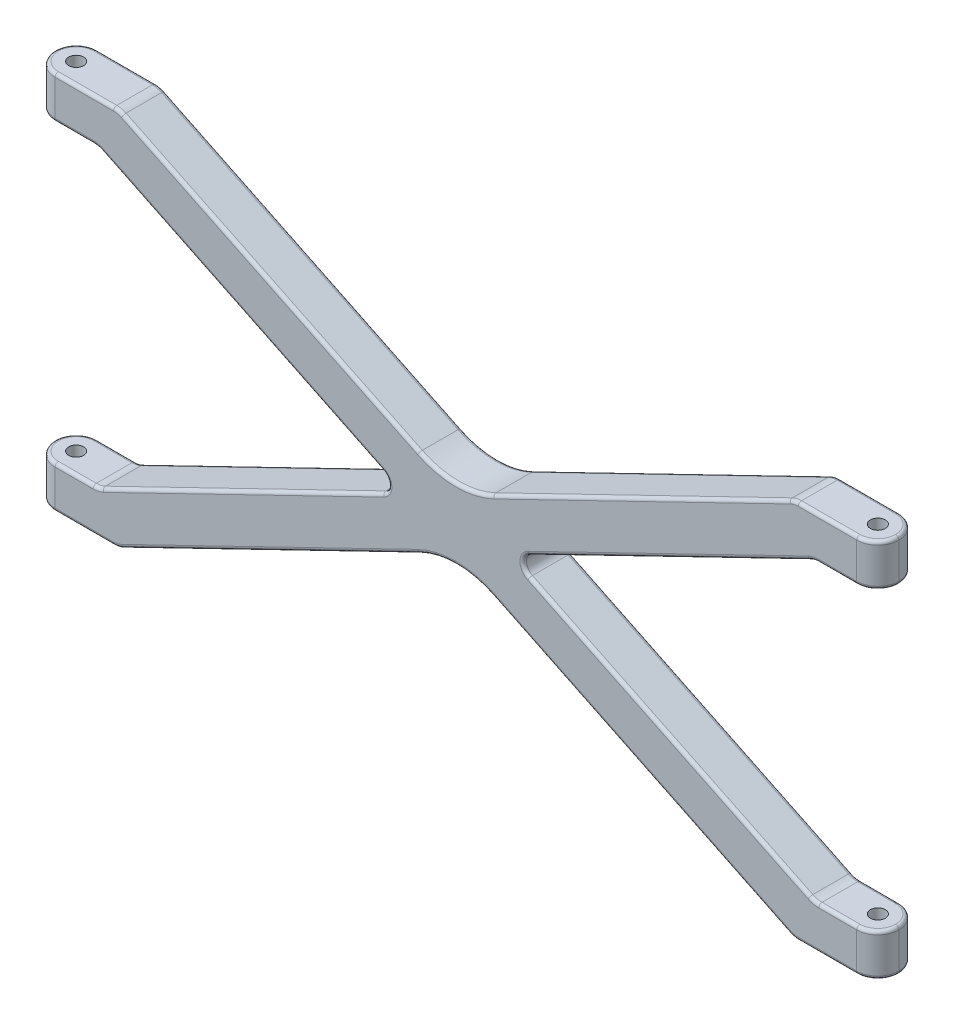
SolidWorks part; units mm, degrees
ref_plane "Front Plane" through (0, 0, 0) normal (0, 0, 1) x (1, 0, 0)
ref_plane "Top Plane" through (0, 0, 0) normal (0, 1, 0) x (1, 0, 0)
ref_plane "Right Plane" through (0, 0, 0) normal (1, 0, 0) x (0, 0, -1)
sketch "Sketch1" plane through (0, 0, 0) normal (0, 0, 1) x (1, 0, 0)
  line L0 (101.6, -57.15) -> (-107.7631, 44.45)
  line L1 (101.6, -57.15) -> (-101.6, -57.15) construction
  line L2 (101.6, -57.15) -> (101.6, 57.15) construction
  line L3 (101.6, 57.15) -> (-101.6, 57.15) construction
  line L4 (-101.6, -57.15) -> (-101.6, 57.15) construction
  line L5 (101.6, -57.15) -> (-101.6, 57.15) construction
  line L6 (101.6, 57.15) -> (-101.6, -57.15) construction
  line L7 (101.6, -57.15) -> (107.7631, -44.45) construction
  line L8 (-107.7631, 44.45) -> (-101.6, 57.15) construction
  line L9 (107.7631, -44.45) -> (-101.6, 57.15)
  line L10 (101.6, -57.15) -> (-101.6, 57.15) construction
  line L11 (-107.7631, 44.45) -> (107.7631, -44.45) construction
  line L12 (-107.7631, -44.45) -> (101.6, 57.15)
  line L13 (-107.7631, -44.45) -> (-101.6, -57.15) construction
  line L14 (101.6, 57.15) -> (107.7631, 44.45) construction
  line L15 (-101.6, -57.15) -> (107.7631, 44.45)
  line L16 (-107.7631, -44.45) -> (107.7631, 44.45) construction
  line L17 (101.6, 57.15) -> (-101.6, -57.15) construction
  line L18 (101.6, 57.15) -> (127, 57.15)
  line L19 (127, 57.15) -> (127, 44.45)
  line L20 (127, 44.45) -> (107.7631, 44.45)
  line L21 (-101.6, 57.15) -> (-127, 57.15)
  line L22 (-127, 57.15) -> (-127, 44.45)
  line L23 (-127, 44.45) -> (-107.7631, 44.45)
  line L24 (-101.6, -57.15) -> (-127, -57.15)
  line L25 (-127, -57.15) -> (-127, -44.45)
  line L26 (-127, -44.45) -> (-107.7631, -44.45)
  line L27 (101.6, -57.15) -> (127, -57.15)
  line L28 (127, -57.15) -> (127, -44.45)
  line L29 (127, -44.45) -> (107.7631, -44.45)
  point P0 (0, 0)
  point P1 (-127, -50.8)
  point P7 (0, 0)
  point P8 (0, 0)
  dimension "D1" = 114.3
  dimension "D2" = 203.2
  dimension "D4" = 12.7
  dimension "D5" = 254
  dimension "D6" = 254
  dimension "D7" = 25.4
extrude "Boss-Extrude1" add sketch "Sketch1" along normal blind 12.7 contours L22 L23 L0 L12 L9 L21 | L20 L19 L18 L12 L9 L15 | L28 L29 L9 L15 L0 L27 | L26 L25 L24 L15 L0 L12 | L0 L15 L9 L12 region at (65.6574, -31.1747, 0) region at (-65.6574, -31.1747, 0) region at (0, 0, 0) region at (-65.6574, 31.1747, 0) region at (65.6574, 31.1747, 0)
fillet "Fillet1" radius 6.35 8 edges at (127, -50.8, 0) (127, -50.8, 12.7) (127, 50.8, 0) (127, 50.8, 12.7) (-127, 50.8, 12.7) (-127, 50.8, 0) (-127, -50.8, 0) (-127, -50.8, 12.7)
sketch "Sketch2" plane through (0, -57.15, 0) normal (0, -1, 0) x (1, 0, 0)
  circle A0 centre (-120.65, 6.35) radius 2.25
  circle A1 centre (120.65, 6.35) radius 2.25
  dimension "D1" = 4.5
extrude "Cut-Extrude1" cut sketch "Sketch2" against normal through all
fillet "Fillet4" radius 25.4 2 edges at (0, 7.8454, 6.35) (0, -7.8454, 6.35)
fillet "Fillet5" radius 3.175 2 edges at (16.1667, 0, 6.35) (-16.1667, 0, 6.35)
fillet "Fillet2" radius 6.35 8 edges at (101.6, -57.15, 6.35) (107.7631, -44.45, 6.35) (107.7631, 44.45, 6.35) (101.6, 57.15, 6.35) (-101.6, 57.15, 6.35) (-107.7631, -44.45, 6.35) (-107.7631, 44.45, 6.35) (-101.6, -57.15, 6.35)
fillet "Fillet3" radius 1 72 edges at (-55.6882, 34.8699, 12.7) (-101.6371, 56.9887, 12.7) (-111.8547, 57.15, 12.7) (-125.1401, 57.15, 10.8401) (-125.1401, 57.15, 1.8599) (-111.8547, 57.15, 0) (-101.6371, 56.9887, 0) (-55.6882, 34.8699, 0) (55.6882, 34.8699, 0) (101.6371, 56.9887, 0) (111.8547, 57.15, 0) (125.1401, 57.15, 1.8599) (125.1401, 57.15, 10.8401) (111.8547, 57.15, 12.7) (101.6371, 56.9887, 12.7) (101.6371, -56.9887, 12.7) (111.8547, -57.15, 12.7) (125.1401, -57.15, 10.8401) (125.1401, -57.15, 1.8599) (111.8547, -57.15, 0) (101.6371, -56.9887, 0) (55.6882, -34.8699, 0) (-55.6882, -34.8699, 0) (-101.6371, -56.9887, 0) (-111.8547, -57.15, 0) (-125.1401, -57.15, 1.8599) (-125.1401, -57.15, 10.8401) (-111.8547, -57.15, 12.7) (-101.6371, -56.9887, 12.7) (-55.6882, -34.8699, 12.7) (64.2515, -23.3346, 12.7) (107.8002, -44.2887, 12.7) (114.9362, -44.45, 12.7) (125.1401, -44.45, 10.8401) (125.1401, -44.45, 1.8599) (114.9362, -44.45, 0) (107.8002, -44.2887, 0) (64.2515, -23.3346, 0) (64.2515, 23.3346, 0) (107.8002, 44.2887, 0) (114.9362, 44.45, 0) (125.1401, 44.45, 1.8599) (125.1401, 44.45, 10.8401) (114.9362, 44.45, 12.7) (107.8002, 44.2887, 12.7) (-64.2515, -23.3346, 12.7) (-107.8002, -44.2887, 12.7) (-114.9362, -44.45, 12.7) (-125.1401, -44.45, 10.8401) (-125.1401, -44.45, 1.8599) (-114.9362, -44.45, 0) (-107.8002, -44.2887, 0) (-64.2515, -23.3346, 0) (-64.2515, 23.3346, 0) (-107.8002, 44.2887, 0) (-114.9362, 44.45, 0) (-125.1401, 44.45, 1.8599) (-125.1401, 44.45, 10.8401) (-114.9362, 44.45, 12.7) (-107.8002, 44.2887, 12.7) (55.6882, 34.8699, 12.7) (55.6882, -34.8699, 12.7) (64.2515, 23.3346, 12.7) (-64.2515, 23.3346, 12.7) (0, 10.6783, 12.7) (0, 10.6783, 0) (0, -10.6783, 0) (0, -10.6783, 12.7) (20.264, 0, 12.7) (20.264, 0, 0) (-20.264, 0, 12.7) (-20.264, 0, 0)
